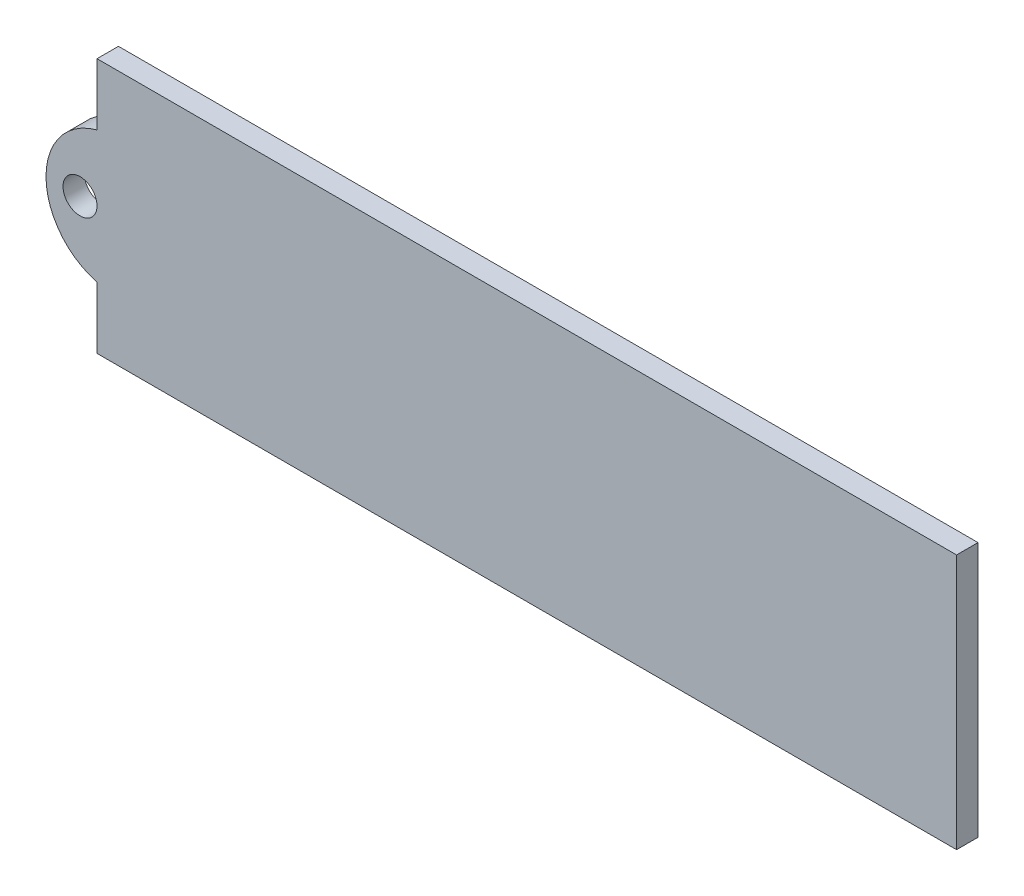
SolidWorks part; units mm, degrees
ref_plane "Front Plane" through (0, 0, 0) normal (0, 0, 1) x (1, 0, 0)
ref_plane "Top Plane" through (0, 0, 0) normal (0, 1, 0) x (1, 0, 0)
ref_plane "Right Plane" through (0, 0, 0) normal (1, 0, 0) x (0, 0, -1)
sketch "Sketch2" plane through (0, 0, 0) normal (0, 0, 1) x (1, 0, 0)
  line L0 (-38.5254, 10.3251) -> (-38.5254, -10.3251)
  line L1 (38.5254, -10.3251) -> (-38.5254, -10.3251)
  line L2 (38.5254, 10.3251) -> (38.5254, -10.3251)
  line L3 (-38.5254, 10.3251) -> (38.5254, 10.3251)
  line L4 (-40.1129, 11.9126) -> (40.1129, 11.9126)
  line L5 (40.1129, 11.9126) -> (40.1129, -11.9126)
  line L6 (40.1129, -11.9126) -> (-40.1129, -11.9126)
  line L7 (-40.1129, 11.9126) -> (-40.1129, -11.9126)
  line L8 (-40.1129, 11.9126) -> (40.1129, -11.9126) construction
  line L9 (40.1129, 11.9126) -> (-40.1129, -11.9126) construction
  line L10 (-38.5254, 10.3251) -> (38.5254, -10.3251) construction
  line L11 (38.5254, 10.3251) -> (-38.5254, -10.3251) construction
  circle A0 centre (-38.5254, 0) radius 6.35
  point P10 (0, 0)
extrude "Boss-Extrude1" add sketch "Sketch2" along normal blind 2 contours L7 A0 | L0 A0 L7 | L0 A0 | A0 L0 L1 L2 L3 | A0 L0 L3 L2 L1 L7 L6 L5 L4 region at (1.4855, 0, 0) region at (-39.3623, 8.3376, 0) region at (-35.8304, 0, 0) region at (-39.315, 0, 0) region at (-42.0966, 0, 0)
sketch "Sketch5" plane through (0, 0, 0) normal (0, 0, -1) x (-1, 0, 0)
  line L0 (43.5335, 0) -> (42.617, -1.5875) construction
  line L1 (43.5335, 0) -> (42.617, -1.5875)
  line L2 (42.617, 1.5875) -> (43.5335, 0) construction
  line L3 (40.7839, 1.5875) -> (42.617, 1.5875) construction
  line L4 (40.7839, -1.5875) -> (39.8674, 0) construction
  line L5 (40.1129, 6.1484) -> (40.1129, 11.9126)
  line L6 (40.1129, 11.9126) -> (-40.1129, 11.9126)
  line L7 (-40.1129, 11.9126) -> (-40.1129, -11.9126)
  line L8 (-40.1129, -11.9126) -> (40.1129, -11.9126)
  line L9 (40.1129, -11.9126) -> (40.1129, -6.1484)
  line L10 (40.1129, 6.1484) -> (40.1129, 11.9126)
  line L11 (40.1129, 11.9126) -> (-40.1129, 11.9126)
  line L12 (-40.1129, 11.9126) -> (-40.1129, -11.9126)
  line L13 (-40.1129, -11.9126) -> (40.1129, -11.9126)
  line L14 (40.1129, -11.9126) -> (40.1129, -6.1484)
  line L15 (39.8674, 0) -> (40.7839, 1.5875) construction
  line L16 (42.617, -1.5875) -> (40.7839, -1.5875) construction
  line L17 (43.5335, 0) -> (42.617, -1.5875)
  line L18 (42.617, 1.5875) -> (43.5335, 0)
  line L19 (40.7839, 1.5875) -> (42.617, 1.5875)
  line L20 (40.7839, -1.5875) -> (39.8674, 0)
  line L21 (39.8674, 0) -> (40.7839, 1.5875)
  line L22 (42.617, -1.5875) -> (40.7839, -1.5875)
  line L23 (40.7839, 1.5875) -> (42.617, -1.5875) construction
  line L24 (40.7839, -1.5875) -> (42.617, 1.5875) construction
  circle A0 centre (41.7005, 0) radius 1.5875
  arc A1 (40.1129, -6.1484) -> (40.1129, 6.1484) centre (38.5254, 0) ccw
  arc A2 (40.1129, -6.1484) -> (40.1129, 6.1484) centre (38.5254, 0) ccw
  dimension "D1" = 0
extrude "Cut-Extrude1" cut sketch "Sketch5" against normal blind 2.54 contours A0 region at (-41.7005, 0, 0)
